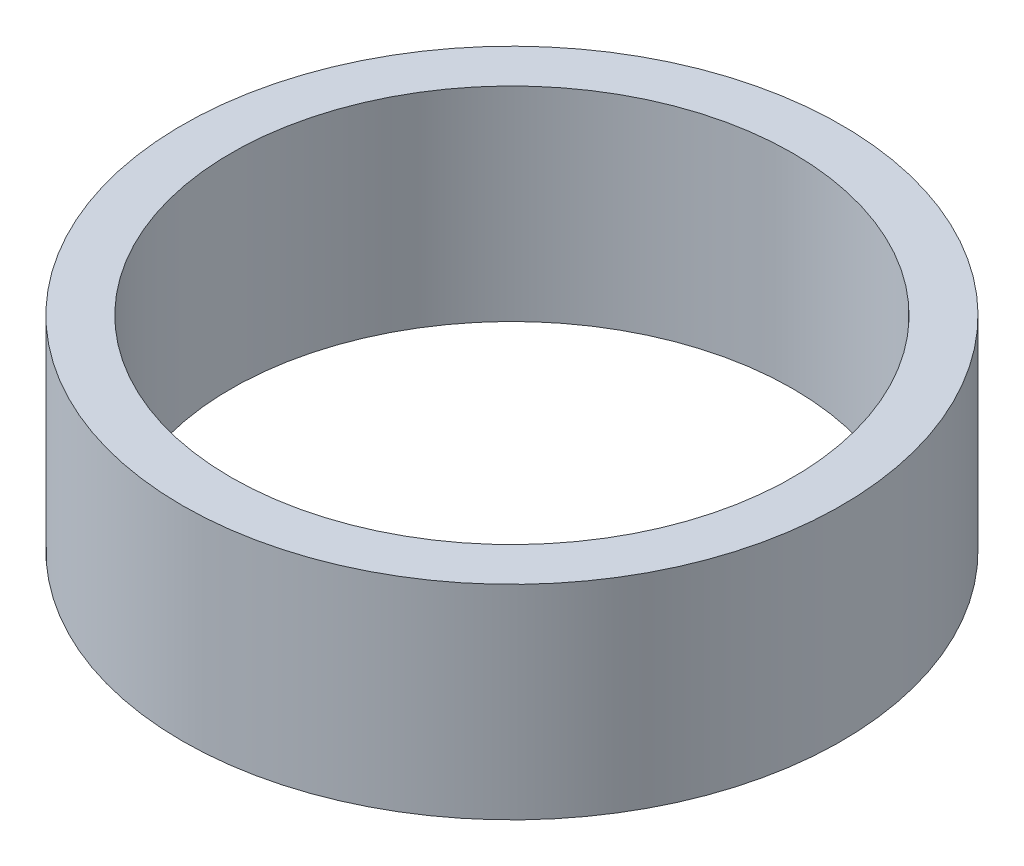
SolidWorks part; units mm, degrees
ref_plane "Front Plane" through (0, 0, 0) normal (0, 0, 1) x (1, 0, 0)
ref_plane "Top Plane" through (0, 0, 0) normal (0, 1, 0) x (1, 0, 0)
ref_plane "Right Plane" through (0, 0, 0) normal (1, 0, 0) x (0, 0, -1)
sketch "Sketch1" plane through (0, 0, 0) normal (0, 1, 0) x (1, 0, 0)
  circle A0 centre (0, 0) radius 35
  dimension "SLEEVE_OD" = 70
extrude "Boss-Extrude1" add sketch "Sketch1" along normal blind 21.6631
sketch "Sketch2" plane through (0, 0, 0) normal (0, 1, 0) x (1, 0, 0)
  circle A0 centre (0, 0) radius 29.8254
  dimension "BORE_D" = 59.6508
extrude "Cut-Extrude1" cut sketch "Sketch2" along normal through all
chamfer "Chamfer1" distance 3.306 angle 45 rebuild error yes
